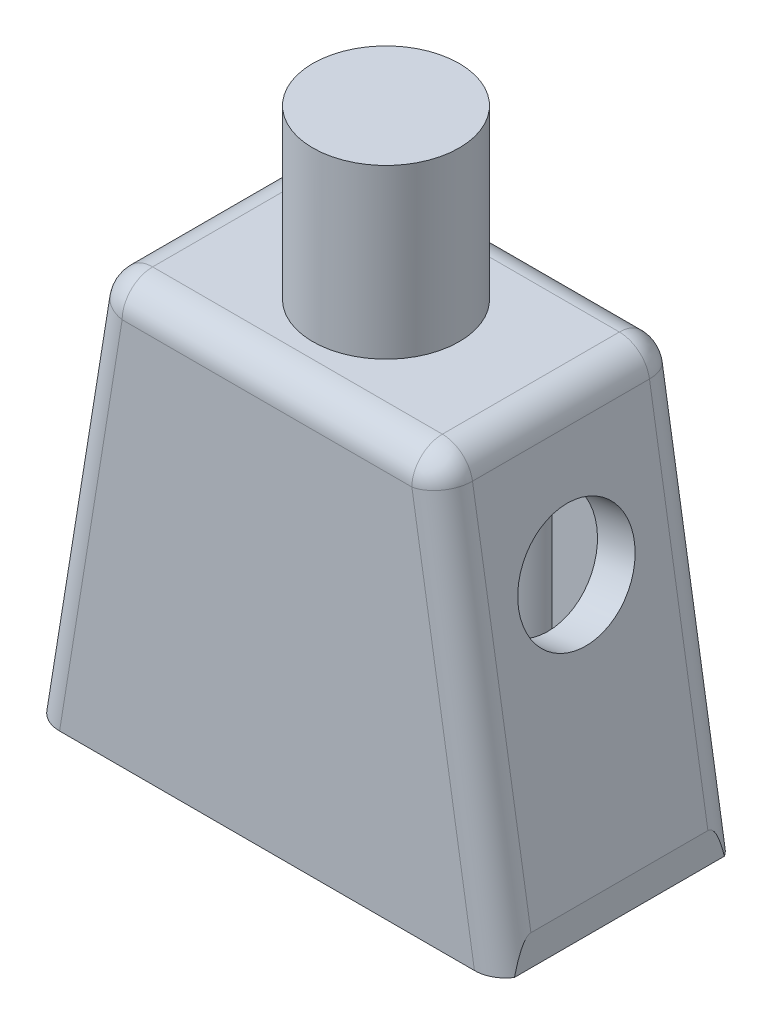
SolidWorks part; units mm, degrees
ref_plane "Front Plane" through (0, 0, 0) normal (0, 0, 1) x (1, 0, 0)
ref_plane "Top Plane" through (0, 0, 0) normal (0, 1, 0) x (1, 0, 0)
ref_plane "Right Plane" through (0, 0, 0) normal (1, 0, 0) x (0, 0, -1)
sketch "Sketch2" plane through (0, 0, 0) normal (0, 0, 1) x (1, 0, 0)
  line L0 (0, 25.9074) -> (0, -26.6172) construction
  line L1 (-7.65, 0) -> (7.65, 0)
  line L2 (7.65, 0) -> (7.65, 1)
  line L3 (7.65, 1) -> (5.5999, 13.7)
  line L4 (5.5999, 13.7) -> (2.3999, 13.7)
  line L8 (-5.5999, 13.7) -> (-2.3999, 13.7)
  line L9 (-7.65, 1) -> (-5.5999, 13.7)
  line L10 (-7.65, 0) -> (-7.65, 1)
  line L11 (-2.3999, 13.7) -> (2.3999, 13.7)
  point P12 (0, 0)
  dimension "D1" = 12.7
  dimension "D2" = 80.83
  dimension "D3" = 1
  dimension "D5" = 3.2
  dimension "D6" = 15.3
extrude "Boss-Extrude1" add sketch "Sketch2" along normal blind 7.8
fillet "Fillet1" radius 1 8 edges at (5.5999, 13.7, 3.9) (0, 13.7, 7.8) (-5.5999, 13.7, 3.9) (0, 13.7, 0) (6.6249, 7.35, 0) (6.6249, 7.35, 7.8) (-6.6249, 7.35, 7.8) (-6.6249, 7.35, 0)
sketch "Sketch3" plane through (0, 13.7, 0) normal (0, 1, 0) x (1, 0, 0)
  line L0 (0, 4.4573) -> (0, -10.6229) construction
  line L1 (-4.7484, -6.8) -> (4.7484, -6.8) construction
  line L2 (4.7484, -1) -> (-4.7484, -1) construction
  circle A0 centre (0, -3.9) radius 2.4
  dimension "D1" = 4.8
  dimension "D2" = 2.9
  dimension "D3" = 2.9
extrude "Boss-Extrude2" add sketch "Sketch3" along normal blind 5.5
ref_plane "Plane1" through (0, 0, 4) normal (0, 0, 1) x (1, 0, 0)
shell "Shell3" thickness 1.25 removed face at (0, 0, 3.9)
sketch "Sketch7" plane through (7.613, 1.229, 0) normal (0.9872, 0.1594, 0) x (0, 0, -1)
  line L0 (-4, 8.415) -> (-4, -8.415) construction
  line L1 (-1, 11.781) -> (-6.8, 11.781) construction
  circle A0 centre (-4, 7.981) radius 1.9
  dimension "D1" = 3.8
  dimension "D2" = 3.8
extrude "Cut-Extrude5" cut sketch "Sketch7" against normal blind 2
mirror "Mirror1" about plane through (0, 0, 0) normal (1, 0, 0) of "Cut-Extrude5"
sketch "Sketch8" plane through (0, 0, 0) normal (0, -1, 0) x (1, 0, 0)
  line L0 (0, 4) -> (0, -1.027) construction
  line L1 (8.415, 4) -> (-8.415, 4) construction
  line L2 (0, 4) -> (0, 9.0509) construction
  line L3 (-7.65, 3.9) -> (-2.7904, 3.9) construction
  line L4 (1.5, 6.55) -> (1.5, 5.6929)
  line L5 (-6.4, 6.55) -> (6.4, 6.55) construction
  line L6 (4.5355, 6.55) -> (-4.5355, 6.55) construction
  line L7 (-1.5, 6.55) -> (-1.5, 5.6929)
  line L8 (-7.65, 7.3416) -> (-7.65, 0.4584) construction
  line L9 (1.5, 1.25) -> (1.5, 2.1071)
  line L10 (-1.5, 1.25) -> (-1.5, 2.1071)
  line L11 (2.7904, 6.55) -> (1.5, 6.55)
  line L12 (-1.5, 6.55) -> (-2.7904, 6.55)
  line L13 (2.7904, 1.25) -> (1.5, 1.25)
  line L14 (-1.5, 1.25) -> (-2.7904, 1.25)
  arc A0 (1.5, 5.6929) -> (2.7904, 6.55) centre (1.5, 7.0929) ccw
  arc A1 (-1.5, 5.6929) -> (-2.7904, 6.55) centre (-1.5, 7.0929) cw
  arc A2 (1.5, 2.1071) -> (2.7904, 1.25) centre (1.5, 0.7071) cw
  arc A3 (-1.5, 2.1071) -> (-2.7904, 1.25) centre (-1.5, 0.7071) ccw
  dimension "D2" = 1.4
  dimension "D3" = 1.2904
  dimension "D1" = 1.5
extrude "Boss-Extrude3" add sketch "Sketch8" against normal up to next
